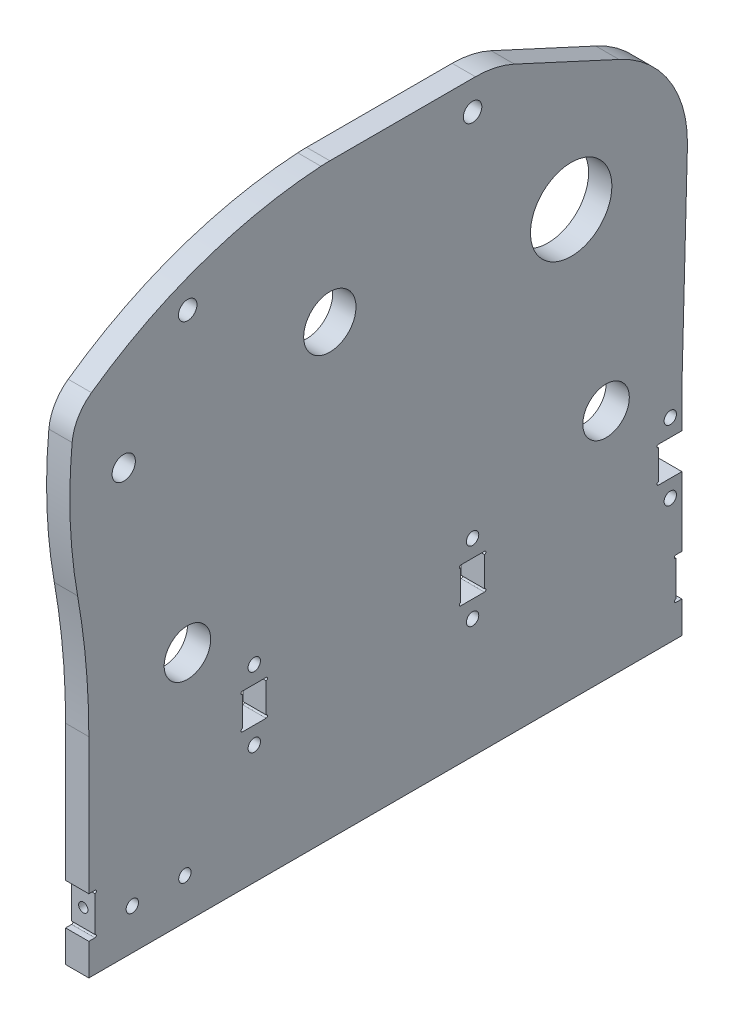
SolidWorks part; units mm, degrees
material "6061-T6 (SS)"
ref_plane "Front Plane" through (0, 0, 0) normal (0, 0, 1) x (1, 0, 0)
ref_plane "Top Plane" through (0, 0, 0) normal (0, 1, 0) x (1, 0, 0)
ref_plane "Right Plane" through (0, 0, 0) normal (1, 0, 0) x (0, 0, -1)
sketch "Sketch1" plane through (0, 0, 0) normal (1, 0, 0) x (0, 0, -1)
  line L0 (0, 44.45) -> (0, 0) construction
  line L1 (-279.4, 44.45) -> (279.4, 44.45)
  line L2 (-279.4, 44.45) -> (-279.4, -44.45)
  line L3 (-279.4, -44.45) -> (279.4, -44.45)
  line L4 (279.4, 44.45) -> (279.4, -44.45)
  line L5 (0, 0) -> (279.4, 0) construction
  dimension "D1" = 558.8
  dimension "D2" = 88.9
extrude "Boss-Extrude1" add sketch "Sketch1" along normal blind 12.7 contours L4 L1 L2 L3 region at (0, 0, 0)
sketch "Sketch2" plane through (12.7, 0, 0) normal (1, 0, 0) x (0, 0, -1)
  line L0 (-279.4, -44.45) -> (279.4, -44.45) construction
  line L1 (-279.4, 44.45) -> (-226.9595, 103.6106)
  line L2 (82.55, 44.45) -> (53.2287, 97.8348)
  line L3 (-203.2, 114.3) -> (25.4, 114.3)
  line L4 (-279.4, 44.45) -> (82.55, 44.45)
  line L5 (-279.4, 44.45) -> (279.4, 44.45) construction
  line L6 (279.4, 44.45) -> (279.4, -44.45) construction
  line L7 (-279.4, 44.45) -> (-318.8009, 0) construction
  line L8 (-318.8009, 0) -> (-279.4, -44.45) construction
  line L9 (-279.4, 44.45) -> (-279.4, -44.45) construction
  line L10 (-279.4, -44.45) -> (-279.4, 0) construction
  line L11 (-279.4, 0) -> (-318.8009, 0) construction
  circle A0 centre (-203.2, 82.55) radius 12.7
  circle A1 centre (25.4, 82.55) radius 12.7
  circle A2 centre (-203.2, 82.55) radius 31.75
  circle A3 centre (25.4, 82.55) radius 31.75
  line M2 (279.4, 44.45) -> (-279.4, 44.45)
  dimension "D1" = 25.4
  dimension "D2" = 63.5
  dimension "D3" = 127
  dimension "D4" = 127
  dimension "D5" = 228.6
  dimension "D6" = 254
  dimension "D7" = 196.85
extrude "Boss-Extrude2" add sketch "Sketch2" against normal blind 12.7 contours A3 L3 A2 L1 L2 M2 | A2 A0 | A3 A1 region at (12.7, 75.2348, 94.7711) region at (12.7, 110.6856, 215.8582) region at (12.7, 90.2167, -55.2842)
sketch "Sketch3" plane through (12.7, 0, 0) normal (1, 0, 0) x (0, 0, -1)
  line L0 (-279.4, -44.45) -> (-318.8009, 0)
  line L1 (-318.8009, 0) -> (-279.4, 44.45)
  line L2 (-279.4, 44.45) -> (-279.4, -44.45)
  line L3 (-318.8009, 0) -> (-279.4, 0) construction
  line L4 (-279.4, 44.45) -> (-226.9595, 103.6106) construction
extrude "Boss-Extrude3" add sketch "Sketch3" against normal blind 12.7
sketch "Sketch4" plane through (12.7, 0, 0) normal (1, 0, 0) x (0, 0, -1)
  line L0 (82.55, 44.45) -> (106.9639, 0)
  line L1 (106.9639, 0) -> (82.55, -44.45)
  line L2 (-279.4, -44.45) -> (279.4, -44.45) construction
  line L3 (0, 0) -> (106.9639, 0) construction
  line L4 (82.55, 44.45) -> (53.2287, 97.8348) construction
  line L5 (82.55, 44.45) -> (279.4, 44.45)
  line L6 (279.4, 44.45) -> (279.4, -44.45)
  line L7 (279.4, -44.45) -> (82.55, -44.45)
  line L8 (82.55, 44.45) -> (82.55, -44.45) construction
extrude "Cut-Extrude1" cut sketch "Sketch4" against normal through all
sketch "Sketch5" plane through (12.7, 0, 0) normal (1, 0, 0) x (0, 0, -1)
  line L0 (-257.0386, -44.45) -> (-257.0386, 69.677)
  line L1 (-279.4, -44.45) -> (82.55, -44.45) construction
  line L2 (-318.8009, 0) -> (-226.9595, 103.6106) construction
  line L4 (-257.0386, -44.45) -> (-279.4, -44.45)
  line L5 (-279.4, -44.45) -> (-318.8009, 0)
  line L6 (-318.8009, 0) -> (-257.0386, 69.677)
  line L7 (66.8114, 73.1049) -> (66.8114, -44.45)
  line L8 (106.9639, 0) -> (53.2287, 97.8348) construction
  line L9 (66.8114, -44.45) -> (82.55, -44.45)
  line L10 (82.55, -44.45) -> (106.9639, 0)
  line L11 (106.9639, 0) -> (66.8114, 73.1049)
  dimension "D1" = 323.85
extrude "Cut-Extrude2" cut sketch "Sketch5" against normal through all
sketch "Sketch6" plane through (12.7, 0, 0) normal (1, 0, 0) x (0, 0, -1)
  line L0 (66.8114, 73.1049) -> (50.3912, 193.3396)
  line L1 (-15.6546, 225.9463) -> (-218.9175, 110.1366)
  line L2 (66.8114, 73.1049) -> (53.2287, 97.8348)
  line L3 (53.2287, 97.8348) -> (25.4, 114.3)
  line L4 (25.4, 114.3) -> (-203.2, 114.3)
  line L5 (-203.2, 114.3) -> (-218.9175, 110.1366)
  circle A0 centre (6.35, 187.325) radius 22.225
  circle A1 centre (6.35, 187.325) radius 44.45
  arc A2 (-203.2, 114.3) -> (-226.9595, 103.6106) centre (-203.2, 82.55) ccw construction
  line M2 (66.8114, 73.1049) -> (53.2287, 97.8348)
  arc M3 (53.2287, 97.8348) -> (25.4, 114.3) centre (25.4, 82.55) ccw
  line M4 (25.4, 114.3) -> (-203.2, 114.3)
  arc M5 (-203.2, 114.3) -> (-226.9595, 103.6106) centre (-203.2, 82.55) ccw
  dimension "D1" = 104.775
  dimension "D3" = 44.45
  dimension "D4" = 88.9
  dimension "D2" = 19.05
extrude "Boss-Extrude4" add sketch "Sketch6" against normal blind 12.7 contours A1 L1 L4 M5 | A1 A0 | A1 L0 M4 M3 M2 region at (12.7, 142.7867, 59.1665) region at (12.7, 190.254, -49.4433)
sketch "Sketch7" plane through (0, 0, 0) normal (-1, 0, 0) x (0, 0, 1)
  line L0 (100.1518, 271.9075) -> (-21.0997, 229.2565)
  line L1 (257.0386, 69.677) -> (196.5842, 227.3108)
  line L2 (257.0386, 69.677) -> (-21.0997, 229.2565)
  line L3 (125.437, 200.025) -> (-6.35, 187.325) construction
  line L4 (257.0386, -44.45) -> (-66.8114, -44.45) construction
  circle A0 centre (125.437, 200.025) radius 76.2
  arc A1 (15.6546, 225.9463) -> (-50.3912, 193.3396) centre (-6.35, 187.325) ccw construction
  circle A2 centre (125.437, 200.025) radius 14.2875
  arc M1 (226.9595, 103.6106) -> (218.9175, 110.1366) centre (203.2, 82.55) ccw
  line M2 (218.9175, 110.1366) -> (15.6546, 225.9463)
  arc M3 (15.6546, 225.9463) -> (-50.3912, 193.3396) centre (-6.35, 187.325) ccw
  line M8 (257.0386, 69.677) -> (226.9595, 103.6106)
  dimension "D1" = 152.4
  dimension "D2" = 244.475
  dimension "D3" = 132.3975
extrude "Boss-Extrude5" add sketch "Sketch7" against normal blind 12.7 contours A0 L0 M3 M2 | A0 A2 M2 | A0 L1 M2 M1 M8 region at (0, 236.4517, 39.4047) region at (0, 214.6063, 133.7447) region at (0, 140.1292, 212.1145)
sketch "Sketch8" plane through (0, 0, 0) normal (-1, 0, 0) x (0, 0, 1)
  line L0 (110.8857, 274.8227) -> (-18.4761, 249.6564)
  line L1 (-66.8114, 73.1049) -> (-69.8272, 185.6237)
  line L2 (-66.8114, 73.1049) -> (-39.6683, 210.1331)
  line L3 (-39.6683, 210.1331) -> (110.8857, 274.8227)
  circle A0 centre (-6.35, 187.325) radius 63.5
  arc A1 (196.5842, 227.3108) -> (100.1518, 271.9075) centre (125.437, 200.025) ccw construction
  arc M3 (196.5842, 227.3108) -> (100.1518, 271.9075) centre (125.437, 200.025) ccw
  line M4 (100.1518, 271.9075) -> (-21.0997, 229.2565)
  arc M5 (-21.0997, 229.2565) -> (-50.3912, 193.3396) centre (-6.35, 187.325) ccw
  line M6 (-50.3912, 193.3396) -> (-66.8114, 73.1049)
extrude "Boss-Extrude6" add sketch "Sketch8" against normal blind 12.7 contours A0 L1 M6 | A0 M4 M6 M5 | A0 L0 M4 M3 region at (0, 256.8682, 40.5472) region at (0, 248.9068, 1.8582) region at (0, 131.4768, -64.3916)
sketch "Sketch9" plane through (12.7, 0, 0) normal (1, 0, 0) x (0, 0, -1)
  line L0 (-257.0386, -44.45) -> (66.8114, -44.45) construction
  line L1 (66.8114, 73.1049) -> (66.8114, -44.45) construction
  line L2 (-257.0386, -44.45) -> (-257.0386, 69.677) construction
  line L3 (-257.0386, 69.677) -> (-196.5842, 227.3108)
  circle A0 centre (-237.9886, 187.325) radius 6.35
  arc A1 (-257.0386, 69.677) -> (-282.4386, 209.55) centre (-654.8656, 69.677) ccw
  arc A2 (-282.4386, 209.55) -> (-130.2888, 276.0704) centre (-114.8056, 33.3925) cw
  arc A3 (-110.8857, 274.8227) -> (-196.5842, 227.3108) centre (-125.437, 200.025) ccw construction
  arc A4 (-196.5842, 227.3108) -> (-130.2888, 276.0704) centre (-125.437, 200.025) cw
  dimension "D1" = 12.7
  dimension "D4" = 349.25
  dimension "D2" = 231.775
  dimension "D3" = 304.8
  dimension "D5" = 254
extrude "Boss-Extrude7" add sketch "Sketch9" against normal blind 12.7
sketch "Sketch10" plane through (12.7, 0, 0) normal (1, 0, 0) x (0, 0, -1)
  line L5 (-257.0386, 69.677) -> (-257.0386, -44.45)
  line L6 (-257.0386, -44.45) -> (66.8114, -44.45)
  line L7 (66.8114, -44.45) -> (66.8114, 73.1049)
  line L8 (66.8114, 73.1049) -> (69.8272, 185.6237)
  line L9 (18.4761, 249.6564) -> (-110.8857, 274.8227)
  line L10 (-257.0386, 69.677) -> (-257.0386, -44.45)
  line L11 (-257.0386, -44.45) -> (66.8114, -44.45)
  line L12 (66.8114, -44.45) -> (66.8114, 73.1049)
  line L13 (66.8114, 73.1049) -> (69.8272, 185.6237)
  line L14 (18.4761, 249.6564) -> (-110.8857, 274.8227)
  circle A0 centre (-125.437, 200.025) radius 76.2
  circle A1 centre (6.35, 187.325) radius 273.7734
  arc A6 (-110.8857, 274.8227) -> (-130.2888, 276.0704) centre (-125.437, 200.025) ccw
  arc A7 (-130.2888, 276.0704) -> (-282.4386, 209.55) centre (-114.8056, 33.3925) ccw
  arc A8 (-257.0386, 69.677) -> (-282.4386, 209.55) centre (-654.8656, 69.677) ccw
  arc A9 (69.8272, 185.6237) -> (18.4761, 249.6564) centre (6.35, 187.325) ccw
  arc A10 (-110.8857, 274.8227) -> (-130.2888, 276.0704) centre (-125.437, 200.025) ccw
  arc A11 (-130.2888, 276.0704) -> (-282.4386, 209.55) centre (-114.8056, 33.3925) ccw
  arc A12 (-257.0386, 69.677) -> (-282.4386, 209.55) centre (-654.8656, 69.677) ccw
  arc A13 (69.8272, 185.6237) -> (18.4761, 249.6564) centre (6.35, 187.325) ccw
  arc M11 (-130.2888, 276.0704) -> (-282.4386, 209.55) centre (-114.8056, 33.3925) ccw
  arc M12 (-282.4386, 209.55) -> (-257.0386, 69.677) centre (-654.8656, 69.677) cw
  dimension "D1" = 0
extrude "Cut-Extrude3" cut sketch "Sketch10" against normal through all contours A1 M11 M12 region at (12.7, 197.6968, 271.7118)
fillet "Fillet2" radius 25.4 1 edges at (6.35, 224.7508, 264.8532)
sketch "Sketch11" plane through (0, 0, 0) normal (-1, 0, 0) x (0, 0, 1)
  line L0 (-66.8114, 73.1049) -> (-66.8114, -44.45) construction
  line L1 (-63.6364, -4.7625) -> (-66.8114, -4.7625)
  line L2 (-63.6364, -4.7625) -> (-63.6364, -26.9875)
  line L3 (-63.6364, -26.9875) -> (-66.8114, -26.9875)
  line L4 (-66.8114, -4.7625) -> (-66.8114, -26.9875)
  line L5 (257.0386, -44.45) -> (257.0386, 69.677) construction
  line L6 (253.8636, -4.7625) -> (257.0386, -4.7625)
  line L7 (253.8636, -4.7625) -> (253.8636, -26.9875)
  line L8 (253.8636, -26.9875) -> (257.0386, -26.9875)
  line L9 (257.0386, -4.7625) -> (257.0386, -26.9875)
  line L10 (253.7366, -4.6355) -> (253.7366, -27.1145)
  line L11 (253.7366, -27.1145) -> (257.1656, -27.1145)
  line L12 (257.1656, -4.6355) -> (257.1656, -27.1145)
  line L13 (253.7366, -4.6355) -> (257.1656, -4.6355)
  line L14 (-63.5094, -4.6355) -> (-63.5094, -27.1145)
  line L15 (-63.5094, -27.1145) -> (-66.9384, -27.1145)
  line L16 (-66.9384, -4.6355) -> (-66.9384, -27.1145)
  line L17 (-63.5094, -4.6355) -> (-66.9384, -4.6355)
  dimension "D1" = 0.127
extrude "Cut-Extrude4" cut sketch "Sketch11" against normal through all
sketch "Sketch12" plane through (12.7, 0, 0) normal (1, 0, 0) x (0, 0, -1)
  line L0 (-253.7366, -4.6355) -> (-253.7366, -27.1145) construction
  line L1 (63.5094, -27.1145) -> (63.5094, -4.6355) construction
  circle A0 centre (-253.7366, -5.4293) radius 0.7937
  circle A1 centre (-253.7366, -26.3208) radius 0.7937
  circle A2 centre (63.5094, -26.3208) radius 0.7937
  circle A3 centre (63.5094, -5.4293) radius 0.7937
  dimension "D1" = 1.5875
extrude "Cut-Extrude5" cut sketch "Sketch12" against normal through all
hole_wizard "1/4 Clearance Hole1" positions "Sketch14" profile "Sketch13" hole size "1/4" standard "ANSI Inch" end condition through all
sketch "Sketch14" plane through (0, 0, 0) normal (-1, 0, 0) x (0, 0, 1)
  point P0 (204.5876, -22.225)
  point P2 (233.2896, -22.225)
sketch "Sketch13" plane through (0, -22.225, 204.5876) normal (0, 1, 0) x (0, 0, 1)
  line L0 (0, 0) -> (0, 12.7)
  line L1 (0, 12.7) -> (3.3782, 12.7)
  line L2 (3.3782, 12.7) -> (3.3782, 0)
  line L5 (3.3782, 0) -> (0, 0)
  line L11 (0, -6.35) -> (0, 107.95) construction
  dimension "Thru Hole Dia." = 6.7564
  dimension "Thru Hole Depth" = 12.7
hole_wizard "1/4-20 Tapped Hole1" positions "Sketch16" profile "Sketch15" tap size "1/4-20" standard "ANSI Inch"
sketch "Sketch16" plane through (0, 0, -63.5094) normal (0, 0, -1) x (-1, 0, 0)
  point P0 (-6.35, -15.875)
sketch "Sketch15" plane through (6.35, -15.875, -63.5094) normal (1, 0, 0) x (0, 1, 0)
  line L0 (0, 0) -> (0, 18.0438)
  line L1 (0, 18.0438) -> (2.5527, 16.51)
  line L2 (2.5527, 16.51) -> (2.5527, 0)
  line L5 (2.5527, 0) -> (0, 0)
  line L10 (0, 18.0438) -> (-2.5527, 16.51) construction
  line L11 (0, -6.35) -> (0, 107.95) construction
  dimension "Tap Drill Dia." = 5.1054
  dimension "Tap Drill Depth" = 16.51
  dimension "Drill Angle" = 118
hole_wizard "1/4-20 Tapped Hole2" positions "Sketch18" profile "Sketch17" tap size "1/4-20" standard "ANSI Inch"
sketch "Sketch18" plane through (0, 0, 253.7366) normal (0, 0, 1) x (1, 0, 0)
  point P0 (6.35, -15.875)
sketch "Sketch17" plane through (6.35, -15.875, 253.7366) normal (1, 0, 0) x (0, -1, 0)
  line L0 (0, 0) -> (0, 18.0438)
  line L1 (0, 18.0438) -> (2.5527, 16.51)
  line L2 (2.5527, 16.51) -> (2.5527, 0)
  line L5 (2.5527, 0) -> (0, 0)
  line L10 (0, 18.0438) -> (-2.5527, 16.51) construction
  line L11 (0, -6.35) -> (0, 107.95) construction
  dimension "Tap Drill Dia." = 5.1054
  dimension "Tap Drill Depth" = 16.51
  dimension "Drill Angle" = 118
sketch "Sketch19" plane through (12.7, 0, 0) normal (1, 0, 0) x (0, 0, -1)
  line L0 (66.8114, 73.1049) -> (66.8114, -4.6355) construction
  line L1 (54.1114, 52.301) -> (66.8114, 52.301)
  line L2 (54.1114, 52.301) -> (54.1114, 33.251)
  line L3 (54.1114, 33.251) -> (66.8114, 33.251)
  line L4 (66.8114, 52.301) -> (66.8114, 33.251)
  line L5 (-160.235, 29.9923) -> (-160.235, 49.2963)
  line L6 (-41.1386, 49.2125) -> (-53.8386, 49.2125)
  line L7 (-41.1386, 49.2125) -> (-41.1386, 30.1625)
  line L8 (-41.1386, 30.1625) -> (-53.8386, 30.1625)
  line L9 (-53.8386, 49.2125) -> (-53.8386, 30.1625)
  line L10 (-173.062, 30.1193) -> (-160.362, 30.1193)
  line L11 (-173.062, 30.1193) -> (-173.062, 49.1693)
  line L12 (-173.062, 49.1693) -> (-160.362, 49.1693)
  line L13 (-160.362, 30.1193) -> (-160.362, 49.1693)
  line L14 (-173.189, 49.2963) -> (-160.235, 49.2963)
  line L15 (-173.189, 29.9923) -> (-173.189, 49.2963)
  line L16 (-173.189, 29.9923) -> (-160.235, 29.9923)
  line L17 (-41.0116, 49.3395) -> (-41.0116, 30.0355)
  line L18 (-41.0116, 30.0355) -> (-53.9656, 30.0355)
  line L19 (-53.9656, 49.3395) -> (-53.9656, 30.0355)
  line L20 (-41.0116, 49.3395) -> (-53.9656, 49.3395)
  line L21 (66.9384, 52.428) -> (66.9384, 33.124)
  line L22 (53.9844, 33.124) -> (66.9384, 33.124)
  line L23 (53.9844, 52.428) -> (53.9844, 33.124)
  line L24 (53.9844, 52.428) -> (66.9384, 52.428)
  dimension "D1" = 0.127
extrude "Cut-Extrude6" cut sketch "Sketch19" against normal through all
sketch "Sketch20" plane through (12.7, 0, 0) normal (1, 0, 0) x (0, 0, -1)
  line L0 (53.9844, 52.428) -> (53.9844, 33.124) construction
  line L1 (-41.0116, 30.0355) -> (-41.0116, 49.3395) construction
  line L2 (-53.9656, 49.3395) -> (-53.9656, 30.0355) construction
  line L3 (-160.235, 29.9923) -> (-160.235, 49.2963) construction
  line L4 (-173.189, 49.2963) -> (-173.189, 29.9923) construction
  line L5 (-41.0116, 49.3395) -> (-53.9656, 49.3395) construction
  circle A0 centre (53.9844, 51.6343) radius 0.7937
  circle A1 centre (53.9844, 33.9178) radius 0.7937
  circle A2 centre (-41.0116, 30.8292) radius 0.7937
  circle A3 centre (-41.0116, 48.5457) radius 0.7937
  circle A4 centre (-53.9656, 48.5457) radius 0.7937
  circle A5 centre (-53.9656, 30.8292) radius 0.7937
  circle A6 centre (-160.235, 30.786) radius 0.7938
  circle A7 centre (-173.189, 30.786) radius 0.7938
  circle A8 centre (-173.189, 48.5025) radius 0.7938
  circle A9 centre (-160.235, 48.5025) radius 0.7938
  dimension "D1" = 1.5875
extrude "Cut-Extrude7" cut sketch "Sketch20" against normal through all
sketch "Sketch23" plane through (12.7, 0, 0) normal (1, 0, 0) x (0, 0, -1)
  line L0 (-125.437, 276.225) -> (-34.7886, 276.225)
  line L1 (-34.7886, 276.225) -> (32.4823, 245.1986)
  line L19 (53.9844, 34.7115) -> (53.9844, 50.8405)
  line L20 (53.9844, 52.428) -> (66.8114, 52.428)
  line L21 (66.8114, 52.428) -> (66.8114, 73.1049)
  line L22 (66.8114, 73.1049) -> (69.8272, 185.6237)
  line L23 (18.4761, 249.6564) -> (-110.8857, 274.8227)
  line L24 (-257.0386, 69.677) -> (-257.0386, -4.6355)
  line L25 (-257.0386, -4.6355) -> (-253.7366, -4.6355)
  line L26 (-253.7366, -6.223) -> (-253.7366, -25.527)
  line L27 (-253.7366, -27.1145) -> (-257.0386, -27.1145)
  line L28 (-257.0386, -27.1145) -> (-257.0386, -44.45)
  line L29 (-257.0386, -44.45) -> (66.8114, -44.45)
  line L30 (66.8114, -44.45) -> (66.8114, -27.1145)
  line L31 (66.8114, -27.1145) -> (63.5094, -27.1145)
  line L32 (63.5094, -25.527) -> (63.5094, -6.223)
  line L33 (63.5094, -4.6355) -> (66.8114, -4.6355)
  line L34 (66.8114, -4.6355) -> (66.8114, 33.124)
  line L35 (66.8114, 33.124) -> (53.9844, 33.124)
  line L36 (53.9844, 34.7115) -> (53.9844, 50.8405)
  line L37 (53.9844, 52.428) -> (66.8114, 52.428)
  line L38 (66.8114, 52.428) -> (66.8114, 73.1049)
  line L39 (66.8114, 73.1049) -> (69.8272, 185.6237)
  line L40 (18.4761, 249.6564) -> (-110.8857, 274.8227)
  line L41 (-257.0386, 69.677) -> (-257.0386, -4.6355)
  line L42 (-257.0386, -4.6355) -> (-253.7366, -4.6355)
  line L43 (-253.7366, -6.223) -> (-253.7366, -25.527)
  line L44 (-253.7366, -27.1145) -> (-257.0386, -27.1145)
  line L45 (-257.0386, -27.1145) -> (-257.0386, -44.45)
  line L46 (-257.0386, -44.45) -> (66.8114, -44.45)
  line L47 (66.8114, -44.45) -> (66.8114, -27.1145)
  line L48 (66.8114, -27.1145) -> (63.5094, -27.1145)
  line L49 (63.5094, -25.527) -> (63.5094, -6.223)
  line L50 (63.5094, -4.6355) -> (66.8114, -4.6355)
  line L51 (66.8114, -4.6355) -> (66.8114, 33.124)
  line L52 (66.8114, 33.124) -> (53.9844, 33.124)
  arc A0 (-110.8857, 274.8227) -> (-130.2888, 276.0704) centre (-125.437, 200.025) ccw construction
  arc A1 (69.8272, 185.6237) -> (18.4761, 249.6564) centre (6.35, 187.325) ccw construction
  arc A14 (53.9844, 34.7115) -> (53.9844, 33.124) centre (53.9844, 33.9178) ccw
  arc A15 (53.9844, 52.428) -> (53.9844, 50.8405) centre (53.9844, 51.6343) ccw
  arc A16 (69.8272, 185.6237) -> (18.4761, 249.6564) centre (6.35, 187.325) ccw
  arc A17 (-110.8857, 274.8227) -> (-130.2888, 276.0704) centre (-125.437, 200.025) ccw
  arc A18 (-130.2888, 276.0704) -> (-255.6045, 231.6548) centre (-114.8056, 33.3925) ccw
  arc A19 (-255.6045, 231.6548) -> (-266.1825, 213.3613) centre (-240.8976, 210.9457) ccw
  arc A20 (-266.1825, 213.3613) -> (-263.1901, 139.3666) centre (6.35, 187.325) ccw
  arc A21 (-257.0386, 69.677) -> (-263.1901, 139.3666) centre (-654.8656, 69.677) ccw
  arc A22 (-253.7366, -6.223) -> (-253.7366, -4.6355) centre (-253.7366, -5.4293) ccw
  arc A23 (-253.7366, -27.1145) -> (-253.7366, -25.527) centre (-253.7366, -26.3208) ccw
  arc A24 (63.5094, -25.527) -> (63.5094, -27.1145) centre (63.5094, -26.3208) ccw
  arc A25 (63.5094, -4.6355) -> (63.5094, -6.223) centre (63.5094, -5.4293) ccw
  arc A26 (53.9844, 34.7115) -> (53.9844, 33.124) centre (53.9844, 33.9178) ccw
  arc A27 (53.9844, 52.428) -> (53.9844, 50.8405) centre (53.9844, 51.6343) ccw
  arc A28 (69.8272, 185.6237) -> (18.4761, 249.6564) centre (6.35, 187.325) ccw
  arc A29 (-110.8857, 274.8227) -> (-130.2888, 276.0704) centre (-125.437, 200.025) ccw
  arc A30 (-130.2888, 276.0704) -> (-255.6045, 231.6548) centre (-114.8056, 33.3925) ccw
  arc A31 (-255.6045, 231.6548) -> (-266.1825, 213.3613) centre (-240.8976, 210.9457) ccw
  arc A32 (-266.1825, 213.3613) -> (-263.1901, 139.3666) centre (6.35, 187.325) ccw
  arc A33 (-257.0386, 69.677) -> (-263.1901, 139.3666) centre (-654.8656, 69.677) ccw
  arc A34 (-253.7366, -6.223) -> (-253.7366, -4.6355) centre (-253.7366, -5.4293) ccw
  arc A35 (-253.7366, -27.1145) -> (-253.7366, -25.527) centre (-253.7366, -26.3208) ccw
  arc A36 (63.5094, -25.527) -> (63.5094, -27.1145) centre (63.5094, -26.3208) ccw
  arc A37 (63.5094, -4.6355) -> (63.5094, -6.223) centre (63.5094, -5.4293) ccw
  dimension "D1" = 0
  dimension "D2" = 101.6
extrude "Boss-Extrude8" add sketch "Sketch23" against normal up to surface (12.7 mm away) contours A29 L40 A28 L1 L0 region at (12.7, 266.8576, 42.276) up to face at (0, 58.9843, 72.62)
hole_wizard "3/8 Clearance Hole1" positions "Sketch22" profile "Sketch21" hole size "3/8" standard "ANSI Inch"
sketch "Sketch22" plane through (0, 0, 0) normal (-1, 0, 0) x (0, 0, 1)
  line L0 (257.0386, -44.45) -> (-66.8114, -44.45) construction
  line L1 (-66.8114, 33.124) -> (-66.8114, -4.6355) construction
  point P0 (47.4886, 260.35)
  point P2 (203.0636, 244.475)
  dimension "D1" = 304.8
  dimension "D2" = 114.3
  dimension "D3" = 269.875
  dimension "D4" = 288.925
sketch "Sketch21" plane through (0, 260.35, 47.4886) normal (0, 1, 0) x (0, 0, 1)
  line L0 (0, 0) -> (0, 15.7295)
  line L1 (0, 15.7295) -> (5.0419, 12.7)
  line L2 (5.0419, 12.7) -> (5.0419, 0)
  line L5 (5.0419, 0) -> (0, 0)
  line L10 (0, 15.7295) -> (-5.0419, 12.7) construction
  line L11 (0, -6.35) -> (0, 107.95) construction
  dimension "Hole Dia." = 10.0838
  dimension "Hole Depth" = 12.7
  dimension "Drill Angle" = 118
fillet "Fillet3" radius 50.8 1 edges at (6.35, 276.225, 34.7886)
hole_wizard "1/4 Clearance Hole2" positions "Sketch25" profile "Sketch24" hole size "1/4" standard "ANSI Inch"
sketch "Sketch25" plane through (12.7, 0, 0) normal (1, 0, 0) x (0, 0, -1)
  point P0 (-166.712, 58.6943)
  point P2 (-166.712, 20.5943)
  point P4 (-47.4886, 20.6375)
  point P6 (-47.4886, 58.7375)
  point P8 (60.4614, 61.826)
  point P10 (60.4614, 23.726)
sketch "Sketch24" plane through (12.7, 58.6943, 166.712) normal (0, 1, 0) x (0, 0, -1)
  line L0 (0, 0) -> (0, 14.7298)
  line L1 (0, 14.7298) -> (3.3782, 12.7)
  line L2 (3.3782, 12.7) -> (3.3782, 0)
  line L5 (3.3782, 0) -> (0, 0)
  line L10 (0, 14.7298) -> (-3.3782, 12.7) construction
  line L11 (0, -6.35) -> (0, 107.95) construction
  dimension "Hole Dia." = 6.7564
  dimension "Hole Depth" = 12.7
  dimension "Drill Angle" = 118
